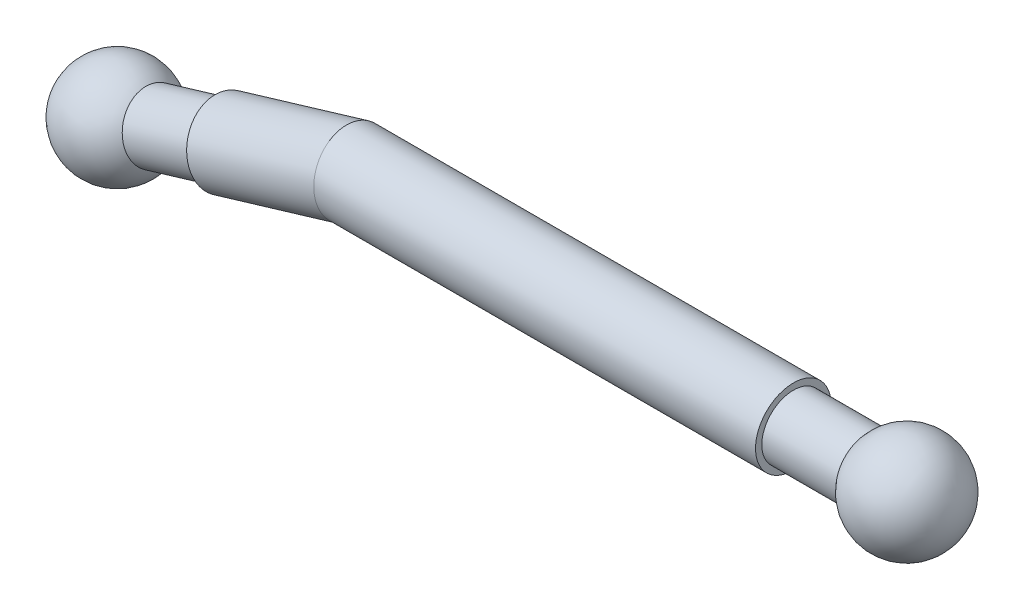
SolidWorks part; units mm, degrees
ref_plane "Front Plane" through (0, 0, 0) normal (0, 0, 1) x (1, 0, 0)
ref_plane "Top Plane" through (0, 0, 0) normal (0, 1, 0) x (1, 0, 0)
ref_plane "Right Plane" through (0, 0, 0) normal (1, 0, 0) x (0, 0, -1)
sketch "Sketch1" plane through (0, 0, 0) normal (1, 0, 0) x (0, 0, -1)
  circle A0 centre (0, 0) radius 3
  dimension "D1" = 6
sketch "Sketch2" plane through (0, 0, 0) normal (0, 0, 1) x (1, 0, 0)
  line L0 (0, 0) -> (-35, 0)
  line L1 (-35, 0) -> (-45, 0) construction
  line L2 (-45, 0) -> (-45, -3) construction
  line L3 (-35, 0) -> (-45, -3)
  dimension "D1" = 35
  dimension "D2" = 10
  dimension "D3" = 3
sweep "Sweep2" add profiles "Sketch1" path "Sketch2"
sketch "Sketch3" plane through (-42.1101, -12.633, 0) normal (-0.9578, -0.2873, 0) x (0, 0, 1)
  circle A0 centre (0, 10.0572) radius 2.5
  dimension "D1" = 5
extrude "Boss-Extrude1" add sketch "Sketch3" along normal blind 6
ref_plane "Plane1" through (-50.7305, -15.2192, 0) normal (-0.9578, -0.2873, 0) x (0, 0, 1)
sketch "Sketch4" plane through (-50.7305, -15.2192, 0) normal (-0.9578, -0.2873, 0) x (0, 0, 1)
  line L0 (0, 14.0572) -> (0, 6.0572) construction
  line L1 (0, 14.0572) -> (0, 6.0572)
  arc A0 (0, 14.0572) -> (0, 6.0572) centre (0, 10.0572) cw
  point P5 (0, 10.0572)
  dimension "D2" = 8
revolve "Revolve1" add sketch "Sketch4" angle 360 about L0
sketch "Sketch5" plane through (0, 0, 0) normal (1, 0, 0) x (0, 0, -1)
  circle A0 centre (0, 0) radius 2.5
  dimension "D1" = 5
extrude "Boss-Extrude2" add sketch "Sketch5" along normal blind 6
ref_plane "Plane2" through (9, 0, 0) normal (1, 0, 0) x (0, 0, -1)
sketch "Sketch6" plane through (9, 0, 0) normal (1, 0, 0) x (0, 0, -1)
  line L0 (0, 4) -> (0, -4)
  arc A0 (0, 4) -> (0, -4) centre (0, 0) cw
  point P5 (0, 0)
  dimension "D2" = 8
revolve "Revolve2" add sketch "Sketch6" angle 360 about L0
